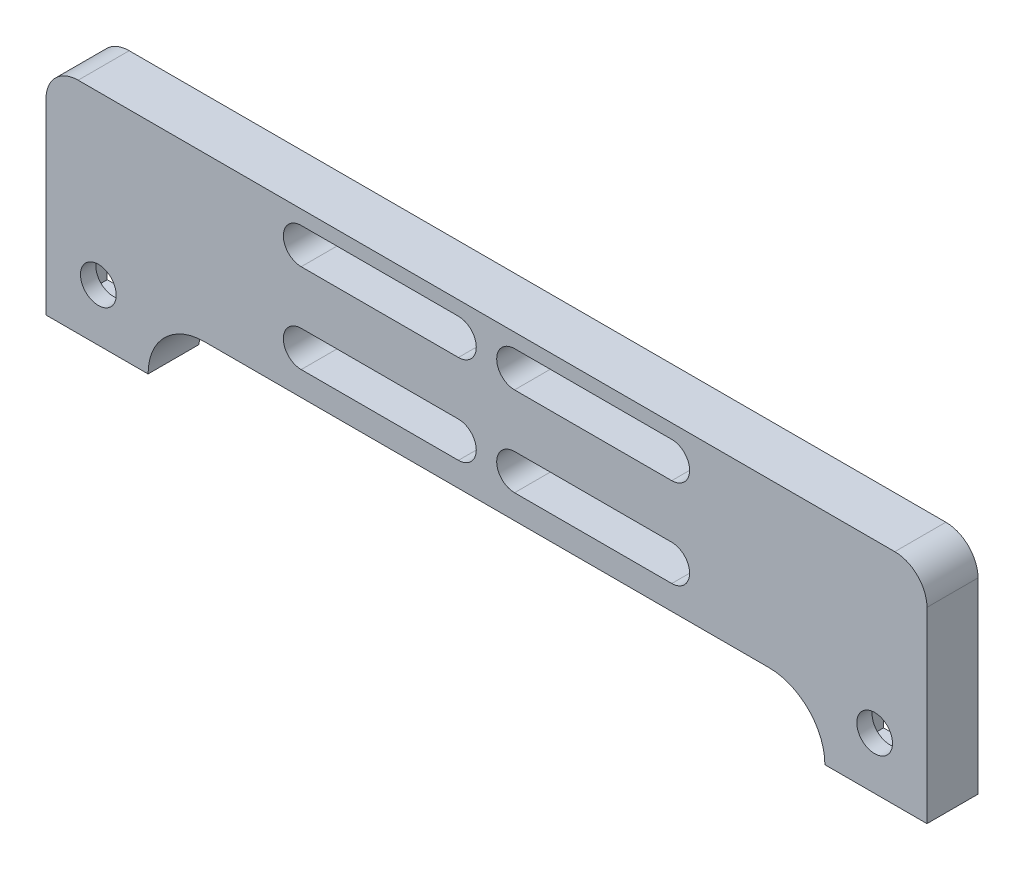
SolidWorks part; units mm, degrees
ref_plane "Front Plane" through (0, 0, 0) normal (0, 0, 1) x (1, 0, 0)
ref_plane "Top Plane" through (0, 0, 0) normal (0, 1, 0) x (1, 0, 0)
ref_plane "Right Plane" through (0, 0, 0) normal (1, 0, 0) x (0, 0, -1)
sketch "Sketch1" plane through (0, 0, 0) normal (0, 0, 1) x (1, 0, 0)
  line L0 (-79.0453, -25.7) -> (80.9547, -25.7) construction
  line L1 (-79.0453, 29.8613) -> (-79.0453, -49.0079) construction
  line L2 (80.9547, 29.8613) -> (80.9547, -49.0079) construction
  line L3 (-85.3453, -25.7) -> (87.2547, -25.7)
  line L4 (87.2547, -25.7) -> (87.2547, 0)
  line L5 (-79.0453, 6.3) -> (80.9547, 6.3)
  line L6 (-85.3453, 0) -> (-85.3453, -25.7)
  line L8 (-83.3453, -11.2) -> (-70.8453, -11.2)
  line L9 (-83.3453, -11.2) -> (-83.3453, -23.7)
  line L10 (-83.3453, -23.7) -> (-70.8453, -23.7)
  line L11 (-70.8453, -11.2) -> (-70.8453, -23.7)
  line L12 (85.2547, -11.2) -> (72.7547, -11.2)
  line L13 (85.2547, -11.2) -> (85.2547, -23.7)
  line L14 (85.2547, -23.7) -> (72.7547, -23.7)
  line L15 (72.7547, -11.2) -> (72.7547, -23.7)
  circle A0 centre (-79.0453, 0) radius 4.3
  circle A1 centre (80.9547, 0) radius 4.3
  arc A2 (-79.0453, 6.3) -> (-85.3453, 0) centre (-79.0453, 0) ccw
  arc A3 (80.9547, 6.3) -> (87.2547, 0) centre (80.9547, 0) cw
  dimension "D2" = 8.6
  dimension "D3" = 8.6
  dimension "D4" = 6.3
  dimension "D5" = 6.3
  dimension "D1" = 160
  dimension "D6" = 32
  dimension "D7" = 2
  dimension "D8" = 2
  dimension "D9" = 12.5
  dimension "D10" = 12.5
  dimension "D11" = 2
  dimension "D12" = 2
  dimension "D13" = 12.5
  dimension "D14" = 12.5
extrude "Boss-Extrude1" add sketch "Sketch1" along normal blind 8
sketch "Sketch2" plane through (0, 0, 8) normal (0, 0, 1) x (1, 0, 0)
  line L0 (-79.0453, 0) -> (80.9547, 0) construction
  line L1 (-35.3453, 6.3) -> (-35.3453, -25.7) construction
  line L2 (80.9547, 6.3) -> (-79.0453, 6.3) construction
  line L3 (-85.3453, -25.7) -> (87.2547, -25.7) construction
  line L4 (-70.8453, -17.45) -> (72.7547, -17.45) construction
  line L5 (-70.8453, -23.7) -> (-70.8453, -11.2) construction
  line L6 (72.7547, -11.2) -> (72.7547, -23.7) construction
  line L7 (37.2547, 6.3) -> (37.2547, -25.7) construction
  line L8 (-85.3453, 0) -> (-85.3453, -25.7) construction
  line L9 (87.2547, -25.7) -> (87.2547, 0) construction
  line L10 (-35.3453, 3.5) -> (37.2547, 3.5)
  line L11 (-35.3453, -3.5) -> (37.2547, -3.5)
  line L12 (-35.3453, -13.95) -> (37.2547, -13.95)
  line L13 (-35.3453, -20.95) -> (34.6432, -20.95)
  line L14 (34.6432, -20.95) -> (37.2547, -20.95)
  arc A0 (-35.3453, 3.5) -> (-35.3453, -3.5) centre (-35.3453, 0) ccw
  arc A1 (37.2547, 3.5) -> (37.2547, -3.5) centre (37.2547, 0) cw
  arc A2 (-35.3453, -13.95) -> (-35.3453, -20.95) centre (-35.3453, -17.45) ccw
  arc A3 (37.2547, -13.95) -> (37.2547, -20.95) centre (37.2547, -17.45) cw
  dimension "D1" = 50
  dimension "D2" = 50
extrude "Cut-Extrude1" cut sketch "Sketch2" against normal blind 8
extrude "Boss-Extrude2" add sketch "Sketch1<2>" along normal blind 10
sketch "Sketch1<2>" plane through (0, 0, 0) normal (0, 0, 1) x (1, 0, 0) same geometry as "Sketch1"
extrude "Cut-Extrude2" cut sketch "Sketch2<2>" against normal through all both and the other way through all
sketch "Sketch2<2>" plane through (0, 0, 8) normal (0, 0, 1) x (1, 0, 0) same geometry as "Sketch2"
sketch "Sketch3" plane through (0, 0, 10) normal (0, 0, 1) x (1, 0, 0)
  line L1 (-83.3453, -11.2) -> (-70.8453, -11.2)
  line L2 (-83.3453, -11.2) -> (-83.3453, -23.7)
  line L3 (-83.3453, -23.7) -> (-70.8453, -23.7)
  line L4 (-70.8453, -11.2) -> (-70.8453, -23.7)
  line L5 (72.7547, -11.2) -> (85.2547, -11.2)
  line L6 (72.7547, -11.2) -> (72.7547, -23.7)
  line L7 (72.7547, -23.7) -> (85.2547, -23.7)
  line L8 (85.2547, -11.2) -> (85.2547, -23.7)
extrude "Boss-Extrude3" add sketch "Sketch3" against normal blind 2
sketch "Sketch4" plane through (0, 0, 10) normal (0, 0, 1) x (1, 0, 0)
  circle A0 centre (-79.0453, 0) radius 4.3
  circle A1 centre (80.9547, 0) radius 4.3
extrude "Boss-Extrude5" add sketch "Sketch4" against normal blind 2
sketch "Sketch5" plane through (0, 0, 10) normal (0, 0, 1) x (1, 0, 0)
  line L0 (0.9547, 3.5) -> (0.9547, -20.95) construction
  line L1 (37.2547, 3.5) -> (-35.3453, 3.5) construction
  line L2 (-35.3453, -20.95) -> (37.2547, -20.95) construction
  line L3 (-38.8453, -17.45) -> (40.7547, -17.45) construction
  line L4 (-38.8453, 0) -> (40.7547, 0) construction
  line L6 (-35.3453, -3.5) -> (37.2547, -3.5) construction
  line L7 (-4.5453, 3.5) -> (6.4547, 3.5)
  line L8 (-4.5453, -3.5) -> (6.4547, -3.5)
  arc A0 (-35.3453, -13.95) -> (-35.3453, -20.95) centre (-35.3453, -17.45) ccw construction
  arc A1 (37.2547, -20.95) -> (37.2547, -13.95) centre (37.2547, -17.45) ccw construction
  arc A2 (-35.3453, 3.5) -> (-35.3453, -3.5) centre (-35.3453, 0) ccw construction
  arc A3 (37.2547, -3.5) -> (37.2547, 3.5) centre (37.2547, 0) ccw construction
  arc A4 (-4.5453, 3.5) -> (-4.5453, -3.5) centre (-4.5453, 0) cw
  arc A5 (6.4547, 3.5) -> (6.4547, -3.5) centre (6.4547, 0) ccw
  point P22 (-4.5453, 0)
  point P23 (6.4547, 0)
  dimension "D1" = 5.5
  dimension "D2" = 5.5
extrude "Boss-Extrude6" add sketch "Sketch5" against normal blind 10
sketch "Sketch6" plane through (0, 0, 10) normal (0, 0, 1) x (1, 0, 0)
  line L0 (0.9547, -13.95) -> (0.9547, -20.95) construction
  line L1 (37.2547, -13.95) -> (-35.3453, -13.95) construction
  line L2 (-35.3453, -20.95) -> (37.2547, -20.95) construction
  line L3 (-38.8453, -17.45) -> (40.7547, -17.45) construction
  line L4 (-4.5453, -13.95) -> (6.4547, -13.95)
  line L5 (-4.5453, -20.95) -> (6.4547, -20.95)
  arc A0 (-35.3453, -13.95) -> (-35.3453, -20.95) centre (-35.3453, -17.45) ccw construction
  arc A1 (37.2547, -20.95) -> (37.2547, -13.95) centre (37.2547, -17.45) ccw construction
  arc A2 (-4.5453, -13.95) -> (-4.5453, -20.95) centre (-4.5453, -17.45) cw
  arc A3 (6.4547, -13.95) -> (6.4547, -20.95) centre (6.4547, -17.45) ccw
  point P14 (6.4547, -17.45)
  point P15 (-4.5453, -17.45)
  dimension "D1" = 5.5
  dimension "D2" = 5.5
extrude "Boss-Extrude7" add sketch "Sketch6" against normal blind 10
sketch "Sketch7" plane through (0, 0, 10) normal (0, 0, 1) x (1, 0, 0)
  line L0 (-85.3453, -25.7) -> (-85.3453, -36.7)
  line L1 (-85.3453, -36.7) -> (-65.3453, -36.7)
  line L2 (87.2547, -25.7) -> (87.2547, -36.7)
  line L3 (87.2547, -36.7) -> (67.2547, -36.7)
  line L4 (-85.3453, -25.7) -> (87.2547, -25.7) construction
  line L5 (-85.3453, -25.7) -> (-54.3453, -25.7)
  line L6 (87.2547, -25.7) -> (56.2547, -25.7)
  arc A0 (-65.3453, -36.7) -> (-54.3453, -25.7) centre (-54.3453, -36.7) cw
  arc A1 (67.2547, -36.7) -> (56.2547, -25.7) centre (56.2547, -36.7) ccw
  point P7 (-54.3453, -36.7)
  point P9 (56.2547, -36.7)
  dimension "D1" = 20
  dimension "D2" = 20
  dimension "D3" = 11
  dimension "D4" = 11
  dimension "D5" = 11
  dimension "D6" = 11
extrude "Boss-Extrude8" add sketch "Sketch7" against normal blind 10
sketch "Sketch8" plane through (0, 0, 0) normal (0, 0, -1) x (-1, 0, 0)
  line L1 (-86.488, -8.1749) -> (-68.3659, -8.1749)
  line L2 (-86.488, -8.1749) -> (-86.488, -30.6799)
  line L3 (-86.488, -30.6799) -> (-68.3659, -30.6799)
  line L4 (-68.3659, -8.1749) -> (-68.3659, -30.6799)
  line L5 (67.3724, -9.1516) -> (84.2875, -9.1516)
  line L6 (67.3724, -9.1516) -> (67.3724, -27.9201)
  line L7 (67.3724, -27.9201) -> (84.2875, -27.9201)
  line L8 (84.2875, -9.1516) -> (84.2875, -27.9201)
extrude "Boss-Extrude9" add sketch "Sketch8" against normal up to surface (10 mm away) up to face at (21.8547, -17.45, 10)
sketch "Sketch12" plane through (0, 0, 0) normal (0, 0, -1) x (-1, 0, 0)
  line L0 (-67.2547, -36.7) -> (-87.2547, -36.7) construction
  line L1 (-85.2547, -34.7) -> (-68.7547, -34.7)
  line L2 (-85.2547, -34.7) -> (-85.2547, -18.2)
  line L3 (-85.2547, -18.2) -> (-68.7547, -18.2)
  line L4 (-68.7547, -34.7) -> (-68.7547, -18.2)
  line L5 (66.8453, -34.7) -> (83.3453, -34.7)
  line L6 (66.8453, -34.7) -> (66.8453, -18.2)
  line L7 (66.8453, -18.2) -> (83.3453, -18.2)
  line L8 (83.3453, -34.7) -> (83.3453, -18.2)
  line L9 (-87.2547, -36.7) -> (-87.2547, 0) construction
  line L10 (85.3453, -36.7) -> (65.3453, -36.7) construction
  line L11 (85.3453, 0) -> (85.3453, -36.7) construction
  dimension "D1" = 16.5
  dimension "D2" = 2
  dimension "D3" = 2
  dimension "D4" = 2
  dimension "D5" = 2
extrude "Cut-Extrude6" cut sketch "Sketch12" against normal blind 7
sketch "Sketch13" plane through (0, 0, 7) normal (0, 0, -1) x (-1, 0, 0)
  line L0 (-85.2547, -18.2) -> (-68.7547, -34.7) construction
  line L1 (83.3453, -18.2) -> (66.8453, -34.7) construction
  circle A0 centre (75.0953, -26.45) radius 3.5
  circle A1 centre (-77.0047, -26.45) radius 3.5
  dimension "D1" = 7
  dimension "D2" = 7
extrude "Cut-Extrude7" cut sketch "Sketch13" against normal blind 7
sketch "Sketch14" plane through (0, 0, 0) normal (0, 0, -1) x (-1, 0, 0)
  line L0 (-0.9547, 6.3) -> (-0.9547, -25.7) construction
  line L1 (-80.9547, 6.3) -> (79.0453, 6.3) construction
  line L2 (54.3453, -25.7) -> (-56.2547, -25.7) construction
  line L3 (-0.9547, -25.7) -> (-0.9547, -9.7) construction
  line L4 (-75.9547, -5.5) -> (-5.9547, -5.5)
  line L5 (4.0453, -5.5) -> (6.7749, -5.5)
  line L6 (74.0453, -5.5) -> (6.7749, -5.5)
  line L7 (4.0453, -11.95) -> (74.0453, -11.95)
  line L8 (-5.9547, -11.95) -> (-75.9547, -11.95)
  arc A0 (-5.9547, -5.5) -> (-5.9547, -11.95) centre (-5.9547, -8.725) cw
  arc A1 (-75.9547, -11.95) -> (-75.9547, -5.5) centre (-75.9547, -8.725) cw
  arc A2 (4.0453, -11.95) -> (4.0453, -5.5) centre (4.0453, -8.725) cw
  arc A3 (74.0453, -5.5) -> (74.0453, -11.95) centre (74.0453, -8.725) cw
  point P6 (-5.9547, -8.725)
  point P8 (4.0453, -8.725)
  dimension "D1" = 5
  dimension "D4" = 70
  dimension "D5" = 70
  dimension "D6" = 70
  dimension "D7" = 5
  dimension "D8" = 5
extrude "Cut-Extrude11" cut sketch "Sketch14" against normal blind 5
